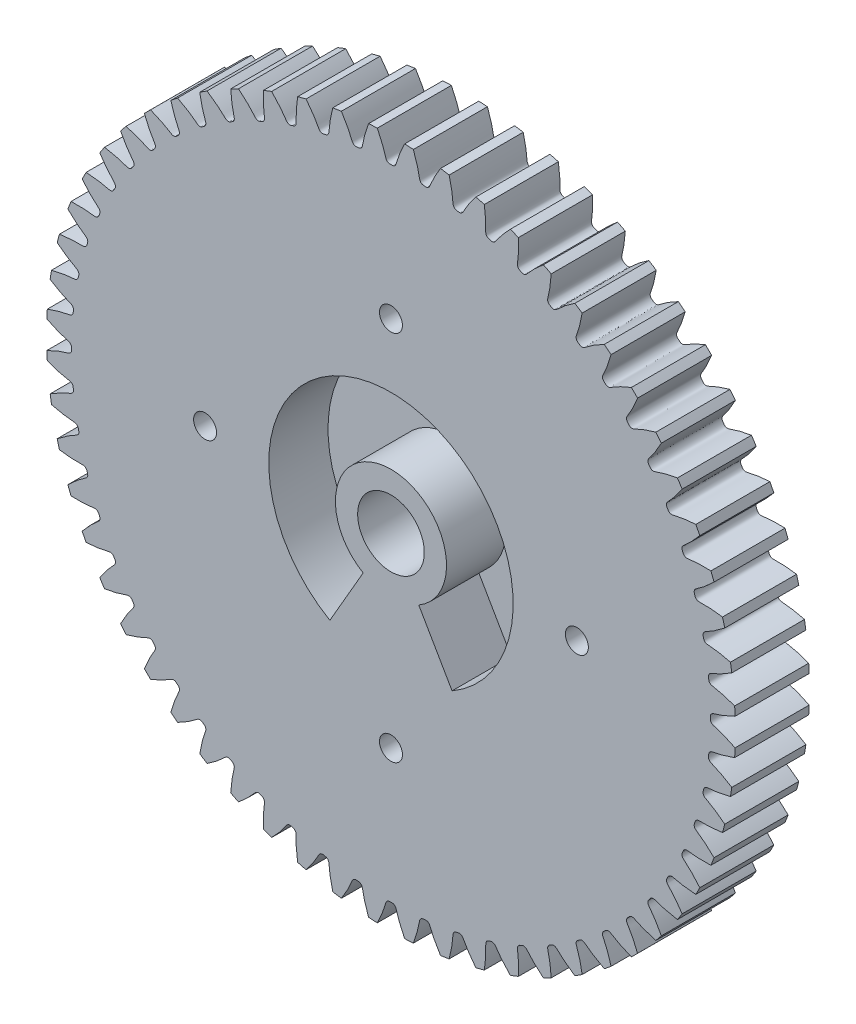
SolidWorks part; units mm, degrees
ref_plane "Front Plane" through (0, 0, 0) normal (0, 0, 1) x (1, 0, 0)
ref_plane "Top Plane" through (0, 0, 0) normal (0, 1, 0) x (1, 0, 0)
ref_plane "Right Plane" through (0, 0, 0) normal (1, 0, 0) x (0, 0, -1)
ref_axis "Axis1" through (0, 0, 5.5) along (0, 0, -1)
sketch "SketchRevolveSpurAssembly01Gear" plane through (0, 0, 0) normal (1, 0, 0) x (0, 0, -1)
  line L0 (0, 0) -> (1, 0) construction
  line L1 (-5, 0) -> (-5, 46.5)
  line L2 (-5, 46.5) -> (5, 46.5)
  line L3 (5, 46.5) -> (5, 0)
  line L4 (5, 0) -> (-5, 0)
  dimension "Side1" = 5
  dimension "OutsideRadius" = 46.5
  dimension "Side2" = 5
revolve "SpurAssembly01Gear" add sketch "SketchRevolveSpurAssembly01Gear" angle 360 about L0
sketch "SketchToothSpurAssembly01Gear" plane through (0, 0, 0) normal (0, 0, 1) x (1, 0, 0)
  arc A0 (46.5369, 1.8824) -> (46.5369, -1.8824) centre (0, 0) cw
  spline S0 degree 3 poles (46.5369, -1.8824) (46.4106, -1.8178) (46.2223, -1.724) (45.9725, -1.6049) (45.7913, -1.5209) (45.614, -1.4411) (45.4406, -1.3655) (45.2713, -1.2938) (45.1061, -1.2261) (44.945, -1.1621) (44.7882, -1.1018) (44.6356, -1.0452) (44.4874, -0.992) (44.3436, -0.9422) (44.2043, -0.8957) (44.0695, -0.8523) (43.9392, -0.8123) (43.7554, -0.7565) (43.5912, -0.7185) (43.4569, -0.6604) (43.397, -0.6284) (43.3333, -0.5856) (43.2647, -0.5249) (43.195, -0.4361) (43.14, -0.3154) (43.1191, -0.1635) (43.1282, 0) (43.1191, 0.1635) (43.14, 0.3154) (43.195, 0.4361) (43.2647, 0.5249) (43.3333, 0.5856) (43.397, 0.6284) (43.4569, 0.6604) (43.5912, 0.7185) (43.7554, 0.7565) (43.9392, 0.8123) (44.0695, 0.8523) (44.2043, 0.8957) (44.3436, 0.9422) (44.4874, 0.992) (44.6356, 1.0452) (44.7882, 1.1018) (44.945, 1.1621) (45.1061, 1.2261) (45.2713, 1.2938) (45.4406, 1.3655) (45.614, 1.4411) (45.7913, 1.5209) (45.9725, 1.6049) (46.2223, 1.724) (46.4106, 1.8178) (46.5369, 1.8824) knots 0 0 0 0 0.051766 0.076686 0.100963 0.124598 0.147592 0.169943 0.191651 0.212718 0.233143 0.252925 0.272065 0.290563 0.308419 0.325633 0.342204 0.358133 0.395729 0.403327 0.411415 0.420483 0.431261 0.444675 0.461387 0.478965 0.5 0.521035 0.538613 0.555325 0.568739 0.579517 0.588585 0.596673 0.604271 0.641867 0.657796 0.674367 0.691581 0.709437 0.727935 0.747075 0.766857 0.787282 0.808349 0.830057 0.852408 0.875402 0.899037 0.923314 0.948234 1 1 1 1
extrude "ToothExtrudeCutSpurAssembly01Gear" cut sketch "SketchToothSpurAssembly01Gear" against normal blind 5 and the other way blind 5
pattern_circular "PatternSpurAssembly01Gear" count 60 over 360 about axis through (0, 0, 5.5) along (0, 0, -1) of "ToothExtrudeCutSpurAssembly01Gear"
sketch "AuxiliarySketchSpurAssembly01Gear" plane through (0, 0, 0) normal (0, 0, 1) x (1, 0, 0)
  circle A0 centre (0, 0) radius 45 construction
  circle A1 centre (0, 0) radius 42.2862 construction
  circle A2 centre (0, 0) radius 43.6372 construction
  circle A3 centre (0, 0) radius 46.5 construction
  circle A4 centre (0, 0) radius 43.125 construction
  dimension "PitchDiameter" = 90
  dimension "BaseDiameter" = 84.5723
  dimension "FormDiameter" = 87.2745
  dimension "MajorDiameter" = 93
  dimension "MinorDiameter" = 86.25
sketch "Sketch3" plane through (0, 0, 5) normal (0, 0, 1) x (1, 0, 0)
  circle A0 centre (0, 0) radius 4
sketch "Sketch4" plane through (0, 0, 5) normal (0, 0, 1) x (1, 0, 0)
  line L0 (0, 0) -> (-9.5, -16.4545) construction
  line L1 (0, 0) -> (9.5, -16.4545) construction
  line L2 (-3.75, -6.4952) -> (-8.25, -14.2894)
  line L3 (3.75, -6.4952) -> (8.25, -14.2894)
  arc A1 (8.25, -14.2894) -> (-8.25, -14.2894) centre (0, 0) ccw
  arc A2 (3.75, -6.4952) -> (-3.75, -6.4952) centre (0, 0) ccw
sketch "Sketch5" plane through (0, 0, -5) normal (0, 0, -1) x (-1, 0, 0)
  circle A0 centre (0, 0) radius 4.5
extrude "Cut-Extrude2" cut sketch "Sketch5" against normal blind 18
sketch "Sketch6" plane through (0, 0, -5) normal (0, 0, -1) x (-1, 0, 0)
  circle A0 centre (25.1, 0) radius 1.55
extrude "Cut-Extrude3" cut sketch "Sketch6" against normal blind 10
pattern_circular "CirPattern2" count 4 over 360 about axis through (0, 0, 5.5) along (0, 0, -1) of "Cut-Extrude3"
extrude "Cut-Extrude4" cut sketch "Sketch4" against normal blind 8
sketch "Sketch7" plane through (0, 0, -5) normal (0, 0, -1) x (-1, 0, 0)
  circle A0 centre (-25.1, 0) radius 3.5
  circle A1 centre (0, 25.1) radius 3.5
  circle A2 centre (25.1, 0) radius 3.5
  circle A3 centre (0, -25.1) radius 3.5
  point P12 (0, 0)
  dimension "D1" = 4
extrude "Cut-Extrude5" cut sketch "Sketch7" against normal blind 3
